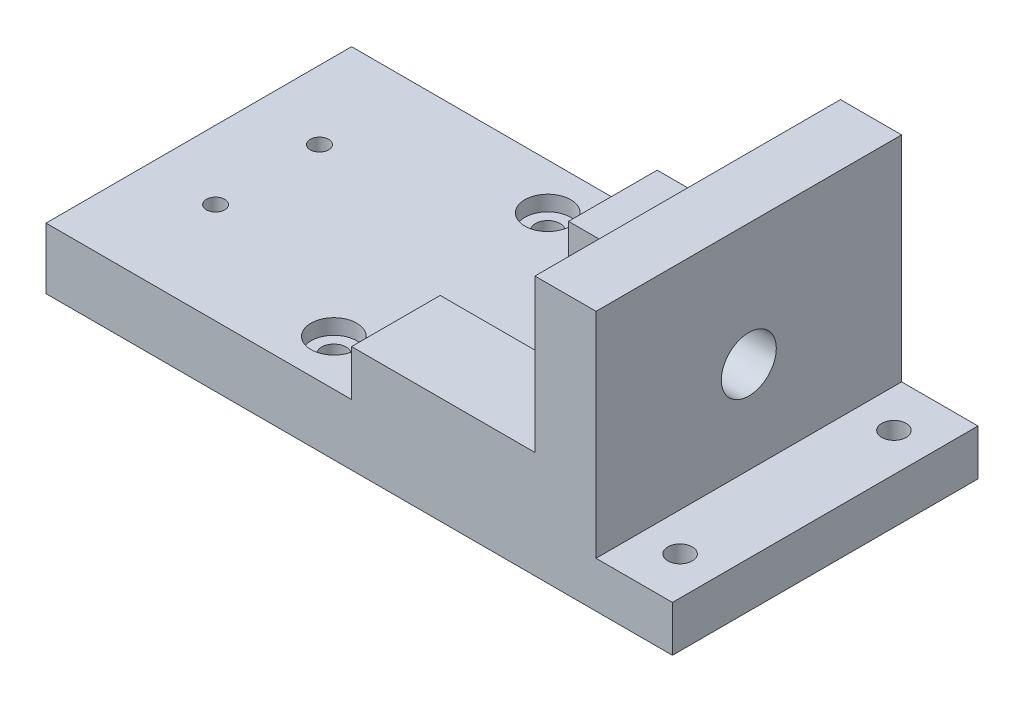
SolidWorks part; units mm, degrees
ref_plane "Front Plane" through (0, 0, 0) normal (0, 0, 1) x (1, 0, 0)
ref_plane "Top Plane" through (0, 0, 0) normal (0, 1, 0) x (1, 0, 0)
ref_plane "Right Plane" through (0, 0, 0) normal (1, 0, 0) x (0, 0, -1)
sketch "Sketch1" plane through (0, 0, 0) normal (0, 0, 1) x (1, 0, 0)
  line L0 (0, 0) -> (0, 15)
  line L1 (0, 15) -> (-25, 15)
  line L2 (-25, 15) -> (-25, 85)
  line L3 (-25, 85) -> (-45, 85)
  line L4 (-45, 85) -> (-45, 35)
  line L5 (-45, 35) -> (-105, 35)
  line L6 (-105, 35) -> (-105, 20)
  line L7 (-105, 20) -> (-205, 20)
  line L8 (-205, 20) -> (-205, 0)
  line L9 (-205, 0) -> (0, 0)
  dimension "D1" = 205
  dimension "D2" = 15
  dimension "D3" = 70
  dimension "D4" = 20
  dimension "D5" = 60
  dimension "D6" = 50
  dimension "D7" = 20
  dimension "D8" = 25
extrude "Boss-Extrude1" add sketch "Sketch1" along normal mid plane 100
sketch "Sketch2" plane through (-25, 0, 0) normal (1, 0, 0) x (0, 0, -1)
  line L0 (-50, 85) -> (50, 85) construction
  circle A1 centre (0, 45) radius 9
  dimension "D1" = 18
  dimension "D2" = 40
extrude "Cut-Extrude1" cut sketch "Sketch2" against normal through all
sketch "Sketch3" plane through (0, 35, 0) normal (0, 1, 0) x (1, 0, 0)
  line L0 (0, 0) -> (-105, 0) construction
  line L2 (-105, -50) -> (-105, 50) construction
  line L3 (-105, 21) -> (-45, 21)
  line L4 (-105, 21) -> (-105, -21)
  line L5 (-105, -21) -> (-45, -21)
  line L6 (-45, 21) -> (-45, -21)
  line L7 (-45, -50) -> (-45, 50) construction
  dimension "D1" = 42
  dimension "D2" = 21
extrude "Cut-Extrude2" cut sketch "Sketch3" against normal up to surface (15 mm away) up to face at (-155, 20, 0)
sketch "Sketch4" plane through (0, 20, 0) normal (0, 1, 0) x (1, 0, 0)
  line L0 (0, 0) -> (-205, 0) construction
  line L1 (-205, -50) -> (-205, 50) construction
  line L4 (0, -50) -> (0, 50) construction
  circle A0 centre (-182.5, 17) radius 3
  circle A1 centre (-125.788, 35) radius 4
  circle A2 centre (-125.788, 35) radius 7.5
  circle A3 centre (-12.5, 35) radius 4
  circle A4 centre (-12.5, 35) radius 7.5
  circle A5 centre (-12.5, -35) radius 4
  circle A6 centre (-12.5, -35) radius 7.5
  circle A7 centre (-125.788, -35) radius 4
  circle A8 centre (-125.788, -35) radius 7.5
  circle A9 centre (-182.5, -17) radius 3
  dimension "D1" = 6
  dimension "D4" = 15
  dimension "D5" = 8
  dimension "D2" = 17
  dimension "D3" = 22.5
  dimension "D6" = 59.5
  dimension "D7" = 35
  dimension "D8" = 12.5
  dimension "D9" = 35
extrude "Cut-Extrude3" cut sketch "Sketch4" against normal through all contours A3 | A1 | A0 | A5 | A7 | A9
extrude "Cut-Extrude4" cut sketch "Sketch4<4>" against normal blind 5 contours A2 | A8
sketch "Sketch4<4>" plane through (0, 20, 0) normal (0, 1, 0) x (1, 0, 0) same geometry as "Sketch4"
